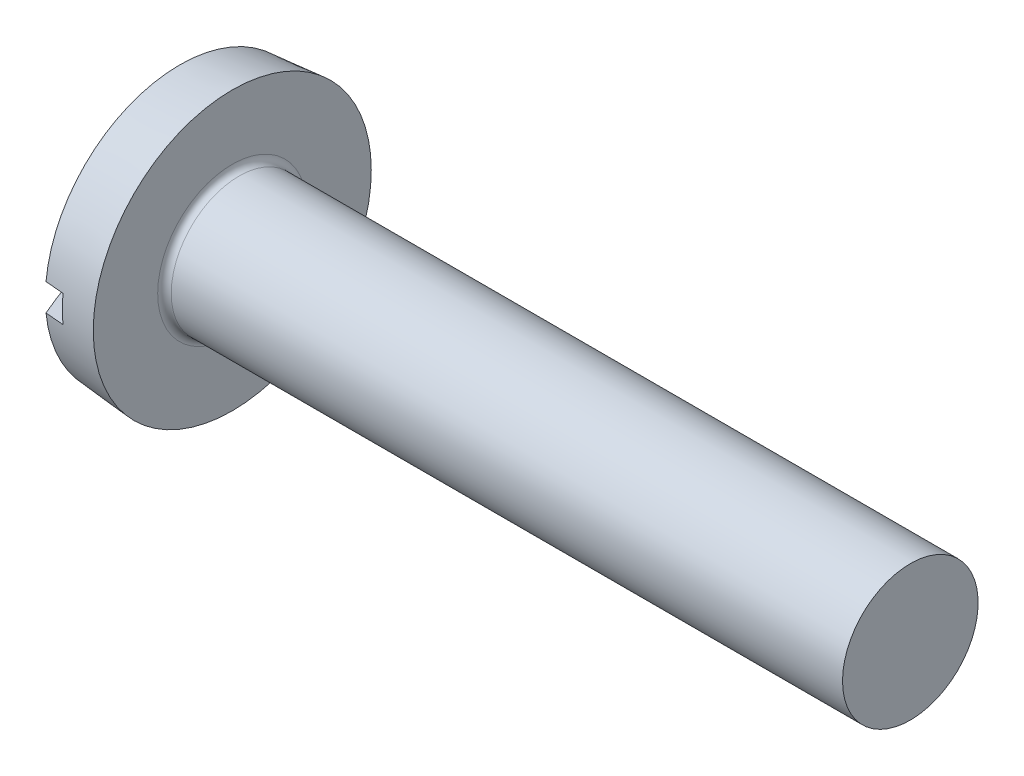
SolidWorks part; units mm, degrees
ref_plane "Front Plane" through (0, 0, 0) normal (0, 0, 1) x (1, 0, 0)
ref_plane "Top Plane" through (0, 0, 0) normal (0, 1, 0) x (1, 0, 0)
ref_plane "Right Plane" through (0, 0, 0) normal (1, 0, 0) x (0, 0, -1)
sketch "BodySke" plane through (0, 0, 0) normal (0, 0, 1) x (1, 0, 0)
  line L0 (0, 0) -> (120.5141, 0) construction
  line L1 (0, 0) -> (0, 50.5629) construction
  line L2 (4.8, 8.2) -> (4.8, 4)
  line L3 (4.8, 4) -> (44.8, 4)
  line L4 (44.8, 4) -> (44.8, 0)
  line L5 (0, 0) -> (44.8, 0)
  line L6 (4.8, 8.2) -> (1.7, 7.9288)
  line L7 (6.05, 10.4207) -> (6.05, -3.1796) construction
  line L8 (14.8, 9.5609) -> (14.8, -6.7938) construction
  arc A0 (0, 0) -> (1.7, 7.9288) centre (19.3399, 0) cw
  point P14 (44.8, 3.3095)
  dimension "Thread_minor" = 6.619
  dimension "Head_height" = 3.1
  dimension "Advance" = 1.25
revolve "BaseBody" add sketch "BodySke" angle 360 about L0
cosmetic thread "ThreadCosmetic" [suppressed]
fillet "Fillet1" radius 0.4 1 edges at (4.8, 0, 4)
sketch "SlotSke" plane through (0, 0, 0) normal (1, 0, 0) x (0, 0, -1)
  line L1 (8.2, 0.8) -> (-8.2, 0.8)
  line L2 (8.2, 0.8) -> (8.2, -0.8)
  line L3 (8.2, -0.8) -> (-8.2, -0.8)
  line L4 (-8.2, 0.8) -> (-8.2, -0.8)
  dimension "D1" = 16.4
  dimension "D2" = 8.2
  dimension "D4" = 0.8
extrude "Slot" cut sketch "SlotSke" along normal blind 2.8
sketch "ThdSchSke" plane through (0, 0, 0) normal (0, 0, 1) x (1, 0, 0)
  line L0 (0, 0) -> (54.7976, 0) construction
  line L1 (44.4013, 4.7973) -> (44.4013, 4)
  line L2 (44.4013, 4.7973) -> (45.1987, 4.7973)
  line L3 (45.1987, 4.7973) -> (45.1987, 4)
  line L4 (45.1987, 4) -> (44.8, 3.3095)
  line L5 (44.8, 3.3095) -> (44.4013, 4)
  line L6 (4.8, 4) -> (44.8, 4) construction
revolve "ThreadSchematic" [suppressed] cut sketch "ThdSchSke" angle 360 about L0
pattern_linear "ThdSchPat" [suppressed] count 24 along (-1, 0, 0) of bodies 103
equation "\"Thread_minor@ThreadCosmetic\" = \"Thread_minor@BodySke\""
equation "\"D1@SlotSke\" = \"Head_dia@BodySke\""
equation "\"D2@SlotSke\" = \"D1@SlotSke\" / 2"
equation "\"D4@SlotSke\" = \"Slot_width@SlotSke\" / 2"
equation "\"Advance@ThdSchPat\" = \"Advance@BodySke\""
equation "\"D1@ThdSchPat\" =  int( \"Thread_length@BodySke\" / \"Advance@BodySke\" ) "
